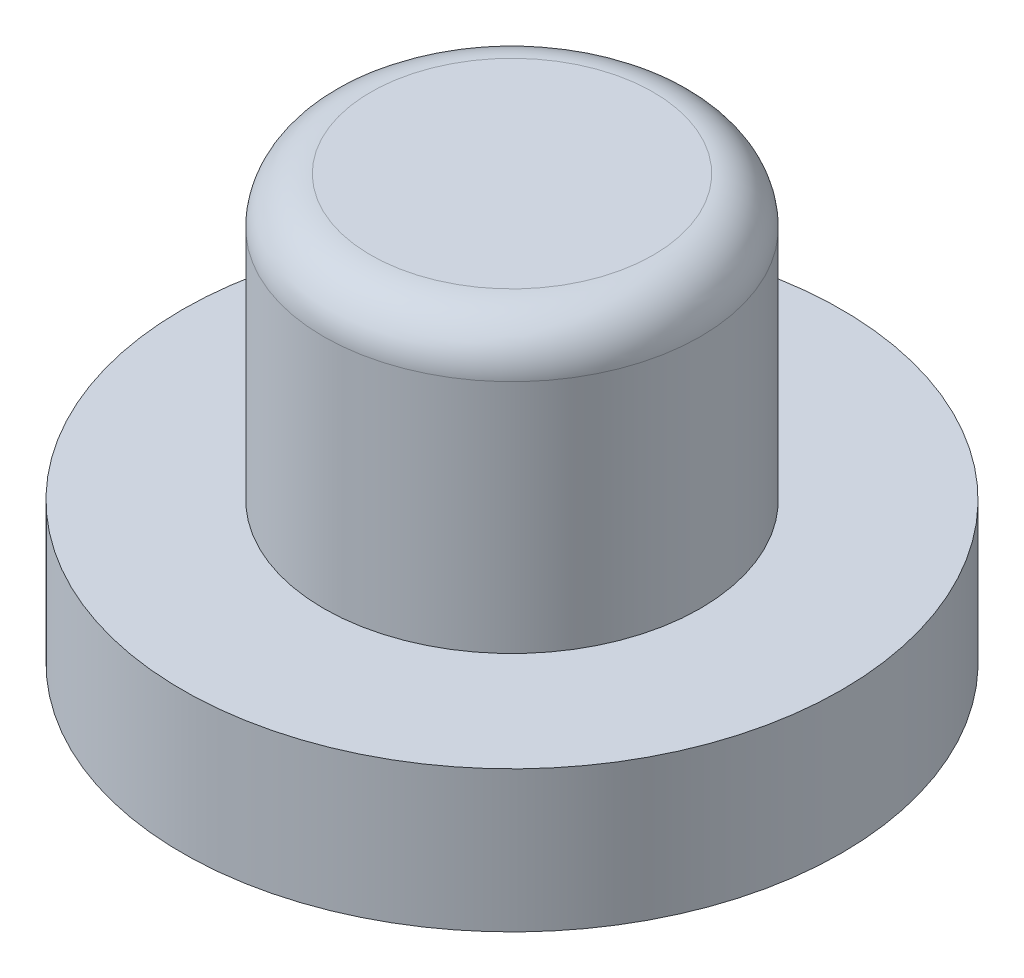
SolidWorks part; units mm, degrees
ref_plane "Front Plane" through (0, 0, 0) normal (0, 0, 1) x (1, 0, 0)
ref_plane "Top Plane" through (0, 0, 0) normal (0, 1, 0) x (1, 0, 0)
ref_plane "Right Plane" through (0, 0, 0) normal (1, 0, 0) x (0, 0, -1)
sketch "Sketch1" plane through (0, 0, 0) normal (0, 0, 1) x (1, 0, 0)
  line L1 (0, 9) -> (4, 9)
  line L2 (4, 9) -> (4, 3)
  line L3 (4, 3) -> (7, 3)
  line L4 (7, 3) -> (7, 0)
  line L6 (0, 9) -> (0, 6.9292) construction
  line L7 (0, 9) -> (0, 0)
  line L10 (0, 0) -> (7, 0)
  dimension "D1" = 4
  dimension "D2" = 3
  dimension "D3" = 6
  dimension "D4" = 3
revolve "Revolve1" add sketch "Sketch1" angle 360 about L6
sketch "Sketch2" plane through (0, 0, 0) normal (0, -1, 0) x (1, 0, 0)
  line L1 (-1.25, -1.75) -> (1.25, -1.75)
  line L2 (-1.25, -1.75) -> (-1.25, 1.75)
  line L3 (-1.25, 1.75) -> (1.25, 1.75)
  line L4 (1.25, -1.75) -> (1.25, 1.75)
  line L5 (-1.25, -1.75) -> (1.25, 1.75) construction
  line L6 (-1.25, 1.75) -> (1.25, -1.75) construction
  point P0 (0, 0)
  dimension "D1" = 2.5
  dimension "D2" = 3.5
extrude "Cut-Extrude1" cut sketch "Sketch2" against normal blind 3 draft 8 contours L3 L4 L1 L2
fillet "Fillet1" radius 1 1 edges at (-4, 9, 0)
